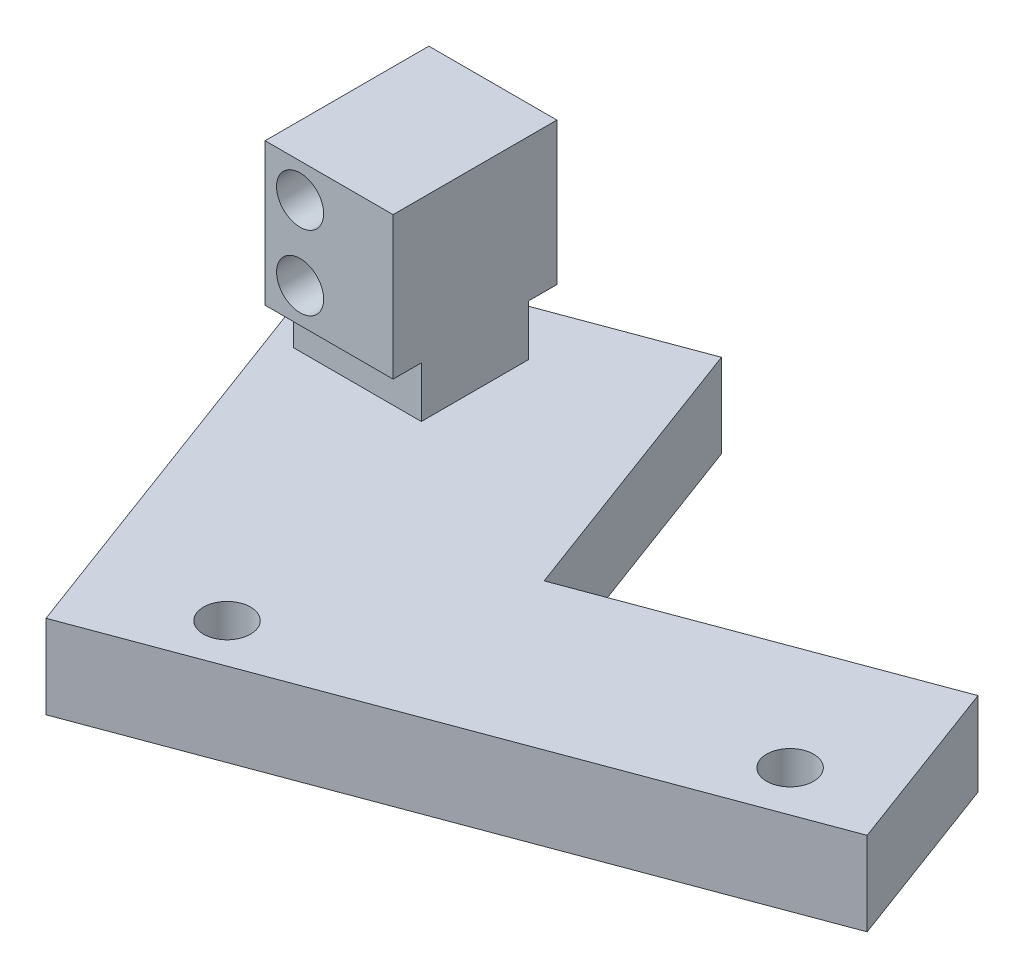
SolidWorks part; units mm, degrees
ref_plane "Front Plane" through (0, 0, 0) normal (0, 0, 1) x (1, 0, 0)
ref_plane "Top Plane" through (0, 0, 0) normal (0, 1, 0) x (1, 0, 0)
ref_plane "Right Plane" through (0, 0, 0) normal (1, 0, 0) x (0, 0, -1)
sketch "Sketch1" plane through (0, 0, 0) normal (0, 0, 1) x (1, 0, 0)
  line L0 (-111.8199, 128.5717) -> (-91.4999, 128.5717)
  line L1 (-122.8766, 128.5659) -> (-97.86, 128.5791) construction
  line L2 (-91.4999, 128.5717) -> (-91.4999, 102.49)
  line L3 (-91.4999, 102.49) -> (-111.8199, 102.49)
  line L4 (-111.8199, 102.49) -> (-111.8199, 128.5717)
  circle A0 centre (-104.0505, 124) radius 3.175
  circle A1 centre (-104.0452, 114) radius 3.175
  dimension "D4" = 6.35
  dimension "D5" = 6.35
  dimension "D1" = 20.32
  dimension "D2" = 6.35
  dimension "D3" = 3.81
extrude "Boss-Extrude1" add sketch "Sketch1" along normal up to surface (22.098 mm away)
ref_plane "Plane1" through (0, 102.49, 0) normal (0, 1, 0) x (1, 0, 0)
sketch "Sketch2" plane through (0, 102.49, 0) normal (0, 1, 0) x (1, 0, 0)
  line L4 (-91.4999, -22.098) -> (-111.8199, -22.098) construction
  line L6 (-93.8327, -66.5977) -> (-13.0724, -36.5641)
  line L9 (-116.8518, -4.6994) -> (-93.8327, -66.5977)
  line L10 (-116.8518, -4.6994) -> (-78.7605, 9.4662)
  line L11 (-78.7605, 9.4662) -> (-64.5949, -28.6251)
  line L12 (-64.5949, -28.6251) -> (-21.9259, -12.757)
  line L13 (-21.9259, -12.757) -> (-13.0724, -36.5641)
  circle A0 centre (-81.3473, -54.66) radius 3.175
  circle A1 centre (-26.1725, -33.8627) radius 3.175
  circle A2 centre (-81.3473, -54.66) radius 3.175 construction
  circle A3 centre (-26.1725, -33.8627) radius 3.175 construction
  dimension "D5" = 15.24
  dimension "D9" = 6.35
  dimension "D10" = 6.35
  dimension "D2" = 25.4
  dimension "D3" = 66.04
  dimension "D4" = 40.64
  dimension "D6" = 40.8958
  dimension "D7" = 86.164
  dimension "D8" = 69.601
extrude "Boss-Extrude2" add sketch "Sketch2" against normal up to surface (11.2786 mm away)
sketch "Sketch3" plane through (-91.4999, 0, 0) normal (1, 0, 0) x (0, 0, -1)
  line L1 (-22.098, 102.49) -> (-18.288, 102.49)
  line L2 (-22.098, 102.49) -> (-22.098, 109.348)
  line L3 (-22.098, 109.348) -> (-18.288, 109.348)
  line L4 (-18.288, 102.49) -> (-18.288, 109.348)
  line L5 (0, 102.49) -> (-3.81, 102.49)
  line L6 (0, 102.49) -> (0, 109.348)
  line L7 (0, 109.348) -> (-3.81, 109.348)
  line L8 (-3.81, 102.49) -> (-3.81, 109.348)
  dimension "D1" = 3.81
  dimension "D2" = 6.858
  dimension "D3" = 3.81
  dimension "D4" = 6.858
extrude "Cut-Extrude1" cut sketch "Sketch3" against normal blind 30.48
sketch "Sketch4" plane through (0, 0, 22.098) normal (0, 0, 1) x (1, 0, 0)
  line L0 (277.0348, 102.49) -> (-277.0348, 102.49) construction
  line L1 (-111.8199, 128.5717) -> (-108.7719, 128.5717)
  line L2 (-111.8199, 128.5717) -> (-111.8199, 102.49)
  line L3 (-111.8199, 102.49) -> (-108.7719, 102.49)
  line L4 (-108.7719, 128.5717) -> (-108.7719, 102.49)
  dimension "D1" = 3.048
extrude "Cut-Extrude2" cut sketch "Sketch4" against normal blind 27.686
